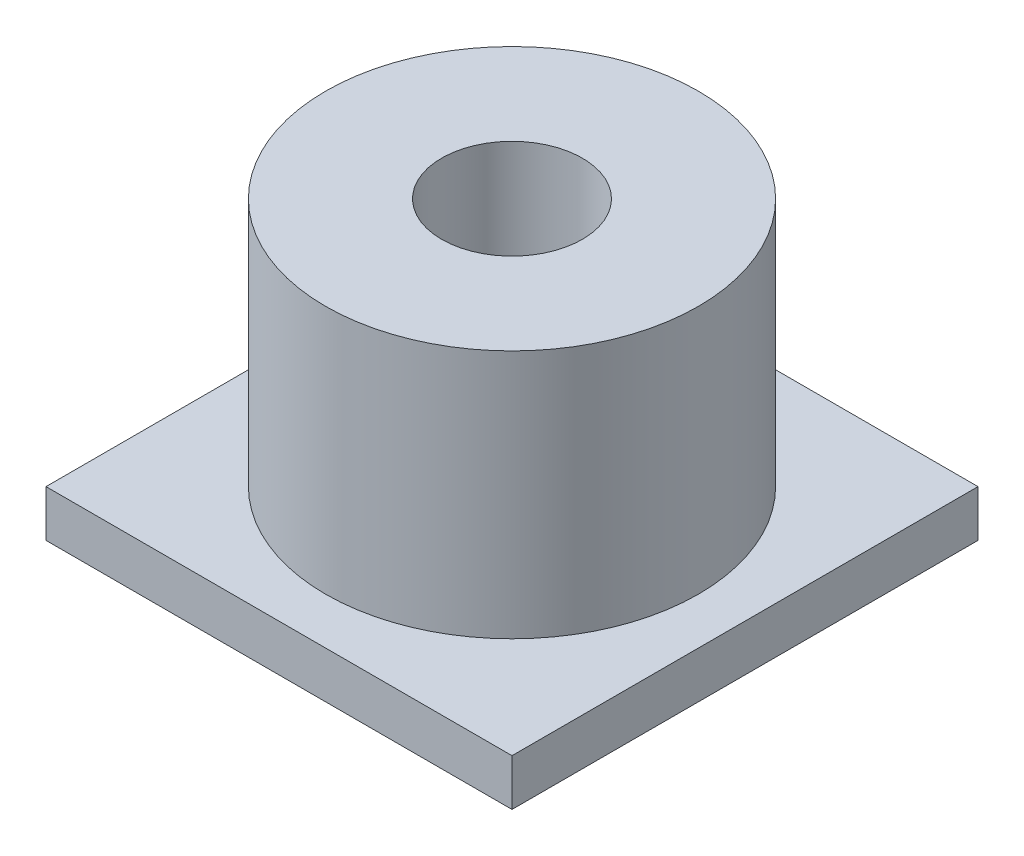
SolidWorks part; units mm, degrees
ref_plane "Front Plane" through (0, 0, 0) normal (0, 0, 1) x (1, 0, 0)
ref_plane "Top Plane" through (0, 0, 0) normal (0, 1, 0) x (1, 0, 0)
ref_plane "Right Plane" through (0, 0, 0) normal (1, 0, 0) x (0, 0, -1)
sketch "Sketch1" plane through (0, 0, 0) normal (0, 1, 0) x (1, 0, 0)
  line L1 (0, 0) -> (10, 0)
  line L2 (0, 0) -> (0, -10)
  line L3 (0, -10) -> (10, -10)
  line L4 (10, 0) -> (10, -10)
  circle A0 centre (5, -5) radius 1.25
  point P4 (0, 0)
  point P8 (5, 0)
  point P9 (0, 0)
  point P10 (0, -5)
  dimension "D3" = 2.5
  dimension "D1" = 10
  dimension "D2" = 10
extrude "Boss-Extrude1" add sketch "Sketch1" along normal blind 1
sketch "Sketch2" plane through (0, 1, 0) normal (0, 1, 0) x (1, 0, 0)
  circle A0 centre (5, -5) radius 1.51
  circle A1 centre (5, -5) radius 1.25 construction
  circle A2 centre (5, -5) radius 4
  dimension "D1" = 3.02
  dimension "D2" = 8
extrude "Boss-Extrude2" add sketch "Sketch2" along normal blind 5.35
